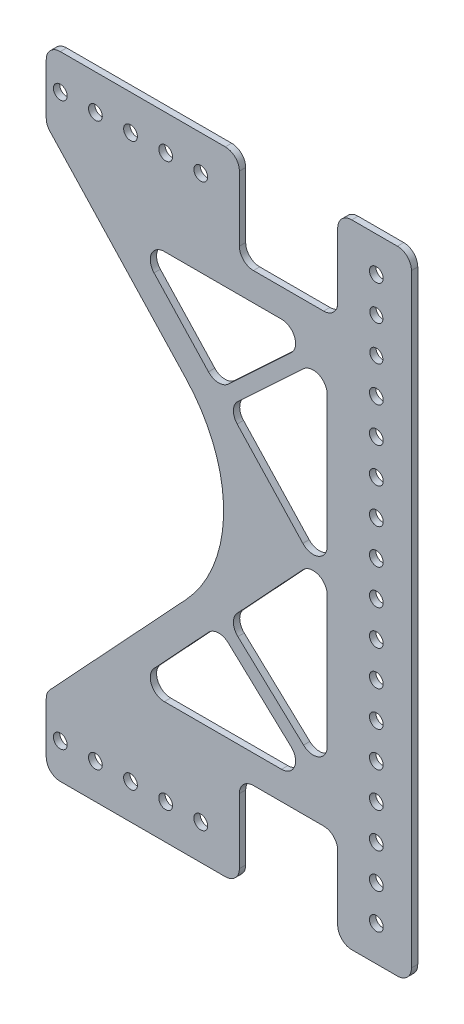
SolidWorks part; units mm, degrees
ref_plane "Front Plane" through (0, 0, 0) normal (0, 0, 1) x (1, 0, 0)
ref_plane "Top Plane" through (0, 0, 0) normal (0, 1, 0) x (1, 0, 0)
ref_plane "Right Plane" through (0, 0, 0) normal (1, 0, 0) x (0, 0, -1)
sketch "Sketch1" plane through (0, 0, 0) normal (0, 0, 1) x (1, 0, 0)
  line L11 (65.4076, 898.4977) -> (48.8976, 898.4977)
  line L12 (43.8176, 893.4177) -> (43.8176, 869.9227)
  line L13 (38.7376, 864.8427) -> (13.3376, 864.8427)
  line L14 (8.2576, 869.9227) -> (8.2576, 893.4177)
  line L15 (3.1776, 898.4977) -> (-56.5124, 898.4977)
  line L16 (-60.2304, 871.6349) -> (-11.0513, 818.8143)
  line L17 (70.4876, 893.4177) -> (70.4876, 784.1977)
  line L18 (-61.5924, 875.0965) -> (-61.5924, 893.4177)
  line L20 (-22.6122, 846.1411) -> (-2.9253, 824.9965)
  line L21 (40.0076, 791.7957) -> (40.0076, 839.4169)
  line L22 (23.5028, 854.6827) -> (-18.8942, 854.6827)
  line L23 (70.4876, 674.9777) -> (70.4876, 784.1977)
  line L24 (65.4076, 669.8977) -> (48.8976, 669.8977)
  line L25 (43.8176, 674.9777) -> (43.8176, 698.4727)
  line L26 (38.7376, 703.5527) -> (13.3376, 703.5527)
  line L27 (8.2576, 698.4727) -> (8.2576, 674.9777)
  line L28 (-60.2304, 696.7606) -> (-11.0513, 749.5812)
  line L29 (3.1776, 669.8977) -> (-56.5124, 669.8977)
  line L30 (-61.5924, 693.2989) -> (-61.5924, 674.9777)
  line L31 (26.9645, 845.8848) -> (4.2543, 824.7402)
  line L32 (7.4596, 754.5529) -> (31.2096, 780.0614)
  line L33 (31.4659, 843.1349) -> (7.716, 821.0222)
  line L34 (7.4596, 813.8426) -> (31.2096, 788.3341)
  line L35 (40.0076, 776.5997) -> (40.0076, 728.9785)
  line L36 (31.4659, 725.2606) -> (7.716, 747.3732)
  line L37 (26.9645, 722.5107) -> (4.2543, 743.6552)
  line L38 (-22.6122, 722.2544) -> (-2.9253, 743.3989)
  line L39 (23.5028, 713.7127) -> (-18.8942, 713.7127)
  arc A1 (65.4076, 898.4977) -> (70.4876, 893.4177) centre (65.4076, 893.4177) cw
  arc A2 (48.8976, 898.4977) -> (43.8176, 893.4177) centre (48.8976, 893.4177) ccw
  arc A3 (43.8176, 869.9227) -> (38.7376, 864.8427) centre (38.7376, 869.9227) cw
  arc A4 (13.3376, 864.8427) -> (8.2576, 869.9227) centre (13.3376, 869.9227) cw
  arc A5 (8.2576, 893.4177) -> (3.1776, 898.4977) centre (3.1776, 893.4177) ccw
  arc A6 (-56.5124, 898.4977) -> (-61.5924, 893.4177) centre (-56.5124, 893.4177) ccw
  circle A7 centre (-31.1124, 885.7977) radius 2.4892
  circle A8 centre (-18.4124, 885.7977) radius 2.4892
  circle A9 centre (-5.7124, 885.7977) radius 2.4892
  circle A11 centre (57.7876, 860.3977) radius 2.3719
  circle A12 centre (57.7876, 847.6977) radius 2.4892
  circle A13 centre (57.7876, 834.9977) radius 2.4892
  circle A14 centre (57.7876, 822.2977) radius 2.4892
  circle A15 centre (57.7876, 809.5977) radius 2.4892
  arc A16 (-60.2304, 871.6349) -> (-61.5924, 875.0965) centre (-56.5124, 875.0965) cw
  arc A17 (31.2096, 788.3341) -> (40.0076, 791.7957) centre (34.9276, 791.7957) ccw
  arc A18 (-22.6122, 846.1411) -> (-18.8942, 854.6827) centre (-18.8942, 849.6027) cw
  arc A19 (65.4076, 669.8977) -> (70.4876, 674.9777) centre (65.4076, 674.9777) ccw
  arc A20 (48.8976, 669.8977) -> (43.8176, 674.9777) centre (48.8976, 674.9777) cw
  arc A21 (43.8176, 698.4727) -> (38.7376, 703.5527) centre (38.7376, 698.4727) ccw
  arc A22 (13.3376, 703.5527) -> (8.2576, 698.4727) centre (13.3376, 698.4727) ccw
  arc A23 (8.2576, 674.9777) -> (3.1776, 669.8977) centre (3.1776, 674.9777) cw
  circle A24 centre (-5.7124, 682.5977) radius 2.4892
  circle A25 centre (-18.4124, 682.5977) radius 2.4892
  circle A26 centre (-31.1124, 682.5977) radius 2.4892
  arc A27 (-60.2304, 696.7606) -> (-61.5924, 693.2989) centre (-56.5124, 693.2989) ccw
  arc A28 (-56.5124, 669.8977) -> (-61.5924, 674.9777) centre (-56.5124, 674.9777) cw
  circle A29 centre (57.7876, 733.3977) radius 2.4892
  circle A30 centre (57.7876, 720.6977) radius 2.4892
  circle A31 centre (57.7876, 707.9977) radius 2.4892
  circle A32 centre (57.7876, 682.5977) radius 2.4892
  circle A33 centre (57.7876, 885.7977) radius 2.4892
  arc A34 (-11.0513, 818.8143) -> (-11.0513, 749.5812) centre (-48.231, 784.1977) cw
  circle A35 centre (57.7876, 771.4977) radius 2.4892
  circle A36 centre (57.7876, 758.7977) radius 2.4892
  circle A37 centre (57.7876, 746.0977) radius 2.4892
  circle A38 centre (-56.5124, 885.7977) radius 2.4892
  circle A39 centre (-43.8124, 885.7977) radius 2.4892
  circle A40 centre (-43.8124, 682.5977) radius 2.4892
  circle A41 centre (-56.5124, 682.5977) radius 2.4892
  arc A42 (7.716, 821.0222) -> (7.4596, 813.8426) centre (11.1776, 817.3043) ccw
  arc A43 (31.4659, 843.1349) -> (40.0076, 839.4169) centre (34.9276, 839.4169) cw
  arc A44 (26.9645, 845.8848) -> (23.5028, 854.6827) centre (23.5028, 849.6027) ccw
  arc A45 (4.2543, 824.7402) -> (-2.9253, 824.9965) centre (0.7927, 828.4582) cw
  arc A46 (31.2096, 780.0614) -> (40.0076, 776.5997) centre (34.9276, 776.5997) cw
  arc A47 (7.716, 747.3732) -> (7.4596, 754.5529) centre (11.1776, 751.0912) cw
  arc A48 (31.4659, 725.2606) -> (40.0076, 728.9785) centre (34.9276, 728.9785) ccw
  arc A49 (26.9645, 722.5107) -> (23.5028, 713.7127) centre (23.5028, 718.7927) cw
  arc A50 (4.2543, 743.6552) -> (-2.9253, 743.3989) centre (0.7927, 739.9373) ccw
  arc A51 (-22.6122, 722.2544) -> (-18.8942, 713.7127) centre (-18.8942, 718.7927) ccw
  circle A52 centre (57.7876, 796.8977) radius 2.4892
  circle A53 centre (57.7876, 784.1977) radius 2.4892
  circle A54 centre (57.7876, 873.0977) radius 2.3719
  circle A55 centre (57.7876, 695.2977) radius 2.4892
  point P14 (70.4876, 784.1977)
  point P17 (45.0876, 784.1977)
  dimension "D1" = 10.16
  dimension "D3" = 5.08
  dimension "D4" = 50.8
  dimension "D5" = 5.08
  dimension "D6" = 5.08
  dimension "D8" = 5.08
  dimension "D11" = 12.7
  dimension "D12" = 12.7
  dimension "D2" = 10.16
  dimension "D7" = 5.08
  dimension "D9" = 3
  dimension "D10" = 2
extrude "Boss-Extrude2" add sketch "Sketch1" along normal blind 2.286 contours L16 A34 L28 A27 L30 A28 L29 A23 L27 A22 L26 A21 L25 A20 L24 A19 L23 L17 A1 L11 A2 L12 A3 L13 A4 L14 A5 L15 A6 L18 A16 A55 A54 A53 A52 A51 L38 A50 L37 A49 L39 A48 L36 A47 L32 region at (15.2139, 784.2164, 0)
sketch "Sketch2" [suppressed] plane through (0, 0, 0) normal (0, 0, -1) x (-1, 0, 0)
  line L0 (-70.4876, 784.1977) -> (29.7113, 784.1977) construction
  line L1 (-70.4876, 674.9777) -> (-70.4876, 893.4177) construction
  circle A0 centre (-26.4815, 826.617) radius 2.54
  circle A1 centre (-30.3527, 804.0119) radius 2.54
  circle A2 centre (-12.2581, 845.8816) radius 2.54
  circle A3 centre (5.9262, 840.3002) radius 2.54
  circle A4 centre (5.9262, 728.0952) radius 2.54
  circle A5 centre (-12.2581, 722.5139) radius 2.54
  circle A6 centre (-30.3527, 764.3835) radius 2.54
  circle A7 centre (-26.4815, 741.7785) radius 2.54
  dimension "D1" = 5.08
sketch "Sketch3" plane through (0, 0, 2.286) normal (0, 0, 1) x (1, 0, 0)
  line L0 (70.4876, -316.1874) -> (70.4876, 49683.8126) construction
  line L1 (-960.1876, 669.8977) -> (49039.8124, 669.8977) construction
  line L2 (70.4876, 674.9777) -> (70.4876, 893.4177) construction
  line L3 (65.4076, 669.8977) -> (48.8976, 669.8977) construction
  point P3 (70.4876, 669.8977)
  point P5 (0, 0)
